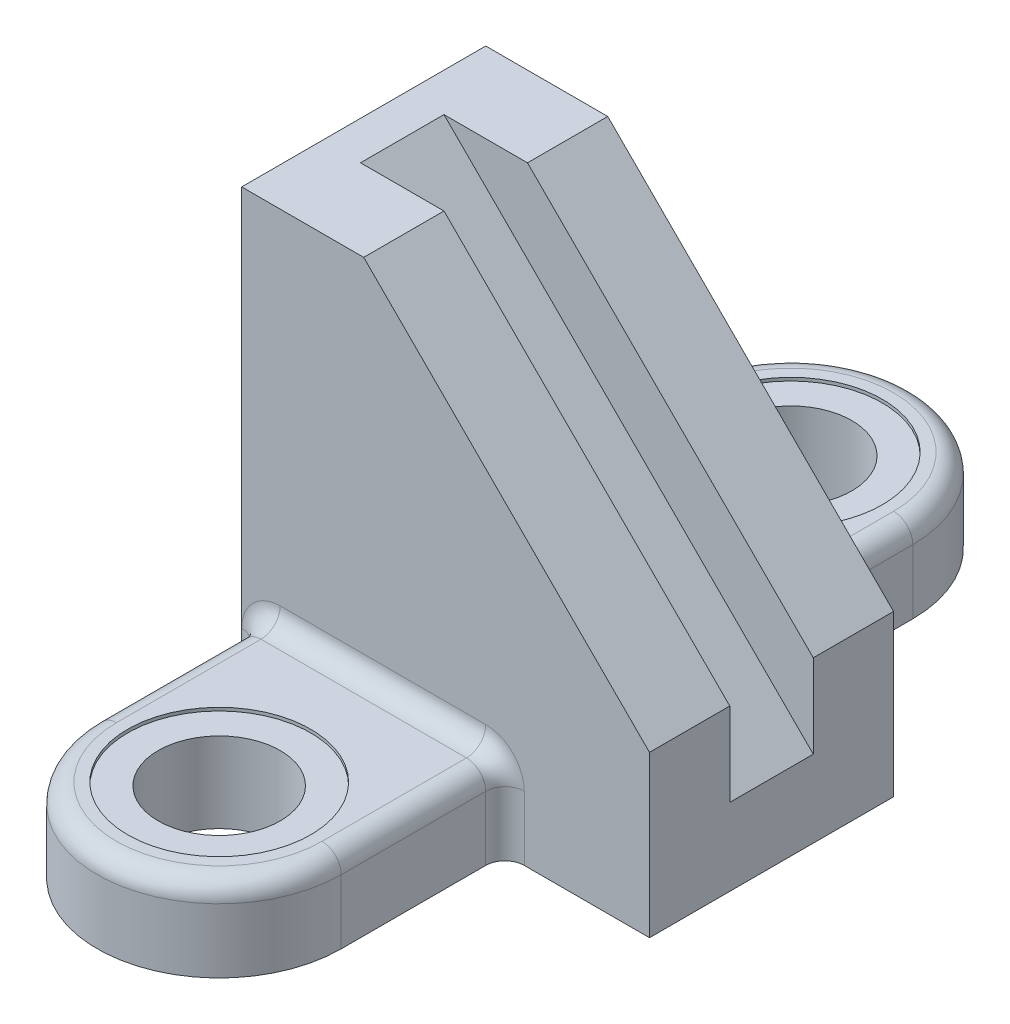
SolidWorks part; units mm, degrees
material "2014 합금"
ref_plane "정면" through (0, 0, 0) normal (0, 0, 1) x (1, 0, 0)
ref_plane "윗면" through (0, 0, 0) normal (0, 1, 0) x (1, 0, 0)
ref_plane "우측면" through (0, 0, 0) normal (1, 0, 0) x (0, 0, -1)
sketch "스케치1" plane through (0, 0, 0) normal (0, 0, 1) x (1, 0, 0)
  line L0 (0, 0) -> (127, 0)
  line L1 (127, 0) -> (127, 50)
  line L2 (127, 50) -> (38, 139)
  line L3 (38, 139) -> (0, 139)
  line L4 (0, 139) -> (0, 0)
  dimension "D1" = 50
  dimension "D2" = 38
  dimension "D3" = 127
  dimension "D4" = 45
extrude "보스-돌출1" add sketch "스케치1" along normal mid plane 76
sketch "스케치2" plane through (0, 139, 0) normal (0, 1, 0) x (1, 0, 0)
  line L0 (38, -38) -> (38, 38) construction
  line L1 (64, -13) -> (12, -13)
  line L2 (64, -13) -> (64, 13)
  line L3 (64, 13) -> (12, 13)
  line L4 (12, -13) -> (12, 13)
  line L5 (64, -13) -> (12, 13) construction
  line L6 (64, 13) -> (12, -13) construction
  point P0 (38, 0)
  point P7 (38, 13)
  dimension "D1" = 26
  dimension "D2" = 26
extrude "컷-돌출1" cut sketch "스케치2" along direction (-0.7071, 0.7071, 0) on the side against the normal through all
sketch "스케치3" plane through (0, 0, 0) normal (0, -1, 0) x (1, 0, 0)
  line L0 (0, 38) -> (127, 38) construction
  line L1 (6, 38) -> (82, 38)
  line L2 (6, 38) -> (6, 89)
  line L3 (6, 89) -> (82, 89) construction
  line L4 (82, 38) -> (82, 89)
  arc A0 (6, 89) -> (82, 89) centre (44, 89) cw
  dimension "D1" = 6
  dimension "D2" = 76
  dimension "D5" = 89
extrude "보스-돌출2" add sketch "스케치3" against normal blind 26
hole_wizard "M36 소켓 머리 캡 나사용 카운터보어1" positions "스케치4" profile "스케치6" counterbore size "M36" standard "KS" end condition through all
sketch "스케치4" plane through (0, 26, 0) normal (0, 1, 0) x (1, 0, 0)
  point P0 (44, -89)
sketch "스케치6" plane through (44, 26, 89) normal (1, 0, 0) x (0, 0, 1)
  line L0 (0, 0) -> (0, 26)
  line L1 (0, 26) -> (19, 26)
  line L3 (19, 26) -> (19, 1)
  line L4 (19, 1) -> (28.5, 1)
  line L5 (28.5, 1) -> (28.5, 0)
  line L7 (28.5, 0) -> (0, 0)
  line L11 (0, -6.35) -> (0, 107.95) construction
  dimension "관통 구멍 지름" = 38
  dimension "관통 구멍 깊이" = 26
  dimension "카운터보어 지름" = 57
  dimension "카운터보어 깊이" = 1
mirror "대칭 복사1" about plane through (0, 0, 0) normal (0, 0, 1) of "보스-돌출2", "M36 소켓 머리 캡 나사용 카운터보어1"
fillet "필렛2" radius 6 12 edges at (6, 13, -38) (6, 13, 38) (44, 26, -38) (44, 26, 38) (6, 26, -63.5) (44, 26, -127) (6, 26, 63.5) (44, 26, 127) (82, 26, -63.5) (82, 13, -38) (82, 26, 63.5) (82, 13, 38)
